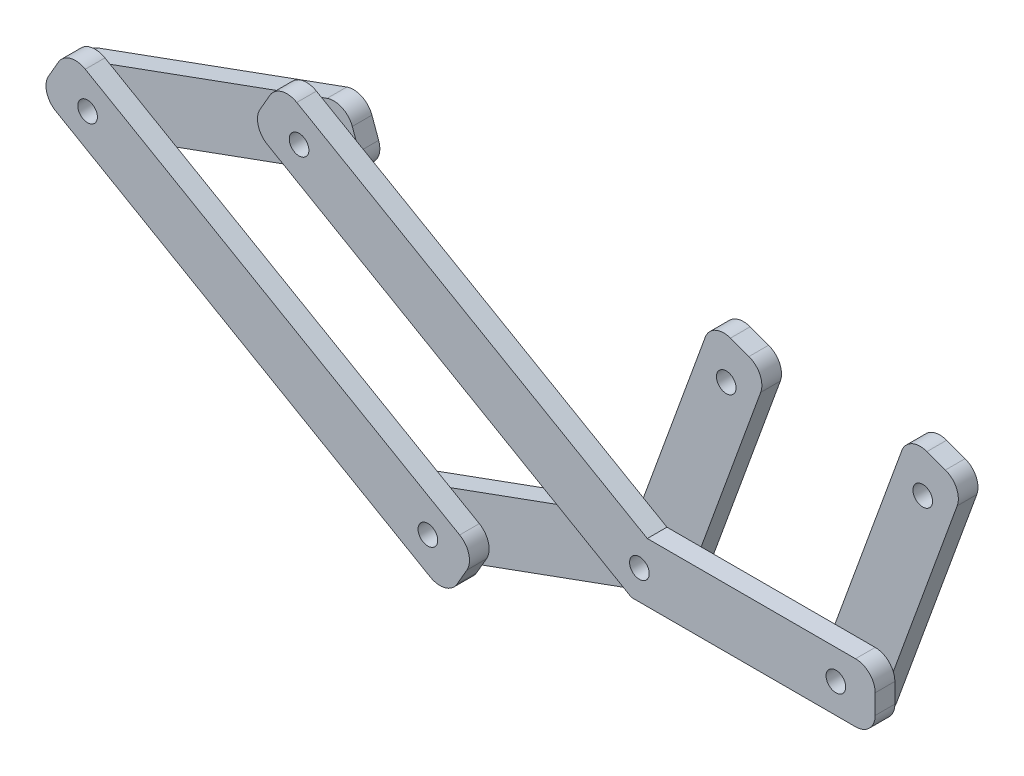
SolidWorks part; units mm, degrees
ref_plane "Front Plane" through (0, 0, 0) normal (0, 0, 1) x (1, 0, 0)
ref_plane "Top Plane" through (0, 0, 0) normal (0, 1, 0) x (1, 0, 0)
ref_plane "Right Plane" through (0, 0, 0) normal (1, 0, 0) x (0, 0, -1)
sketch "Sketch1" plane through (0, 0, 0) normal (0, 0, 1) x (1, 0, 0)
  line L0 (0, 0) -> (-34.202, -93.9693)
  line L1 (0, 0) -> (100, 0)
  line L2 (100, 0) -> (65.798, -93.9693)
  line L8 (65.798, -93.9693) -> (-34.202, -93.9693)
  line L19 (0, 0) -> (68.404, 187.9385)
  line L20 (0, 0) -> (-173.2051, 100)
  line L21 (-34.202, -93.9693) -> (-207.4071, 6.0307)
  line L22 (-34.202, -93.9693) -> (-141.8362, -133.1449)
  line L23 (-141.8362, -133.1449) -> (-315.0412, -33.1449)
  line L24 (-315.0412, -33.1449) -> (-207.4071, 6.0307)
  line L25 (-261.2242, -13.5571) -> (-287.4244, 58.4276)
  line L26 (-287.4244, 58.4276) -> (-173.2051, 100)
  line L27 (-207.4071, 6.0307) -> (-97.22, 46.1356)
  circle A4 centre (-173.2051, 100) radius 48.0396
  dimension "D6" = 200
  dimension "D8" = 130
  dimension "D9" = 150
  dimension "D10" = 96.0793
  dimension "D1" = 200
  dimension "D2" = 110
  dimension "D3" = 100
  dimension "D4" = 200
  dimension "D5" = 100
  dimension "D7" = 200
ref_plane "Plane1" through (0, 0, 180) normal (0, 0, 1) x (1, 0, 0)
sketch "Sketch2" plane through (0, 0, 180) normal (0, 0, 1) x (1, 0, 0)
  line L9 (2.1419, 20.504) -> (11.5389, 17.0838)
  line L10 (-10.6752, 14.5272) -> (-45.9051, -82.2662)
  line L11 (17.5156, 4.2666) -> (-22.4989, -105.6724)
  line L13 (-162.3401, -135.2868) -> (-158.9199, -144.6837)
  line L14 (-156.3634, -122.4697) -> (-45.9051, -82.2662)
  line L15 (-146.1028, -150.6605) -> (-22.4989, -105.6724)
  line L19 (-34.202, -93.9693) -> (-141.8362, -133.1449) construction
  line L20 (0, 0) -> (-34.202, -93.9693) construction
  arc A2 (-146.1028, -150.6605) -> (-158.9199, -144.6837) centre (-149.523, -141.2635) cw
  arc A3 (-162.3401, -135.2868) -> (-156.3634, -122.4697) centre (-152.9432, -131.8666) cw
  arc A4 (-10.6752, 14.5272) -> (2.1419, 20.504) centre (-1.2783, 11.107) cw
  arc A5 (17.5156, 4.2666) -> (11.5389, 17.0838) centre (8.1187, 7.6868) ccw
  circle A6 centre (0, 0) radius 5
  circle A7 centre (-34.202, -93.9693) radius 5
  circle A8 centre (-141.8362, -133.1449) radius 5
  dimension "D4" = 15
  dimension "D1" = 10
  dimension "D5" = 10
  dimension "D9" = 10
  dimension "D10" = 10
  dimension "D2" = 20
  dimension "D3" = 15
  dimension "D6" = 20
  dimension "D7" = 15
  dimension "D8" = 15
extrude "Boss-Extrude1" add sketch "Sketch2" along normal blind 10
move or copy body "Body-Move/Copy1" bodies to move or copy 101 copy no translate (270, 0, 0)
ref_plane "Plane2" through (0, 0, 190) normal (0, 0, 1) x (1, 0, 0)
sketch "Sketch5" plane through (0, 0, 190) normal (0, 0, 1) x (1, 0, 0)
  line L0 (102.1419, 20.504) -> (111.5389, 17.0838)
  line L1 (89.3248, 14.5272) -> (48.2824, -98.2359)
  line L2 (117.5156, 4.2666) -> (76.4732, -108.4965)
  line L3 (54.2591, -111.053) -> (63.656, -114.4732)
  line L4 (100, 0) -> (65.798, -93.9693) construction
  arc A0 (76.4732, -108.4965) -> (63.656, -114.4732) centre (67.0762, -105.0763) cw
  arc A1 (48.2824, -98.2359) -> (54.2591, -111.053) centre (57.6793, -101.6561) ccw
  arc A2 (89.3248, 14.5272) -> (102.1419, 20.504) centre (98.7217, 11.107) cw
  arc A3 (111.5389, 17.0838) -> (117.5156, 4.2666) centre (108.1187, 7.6868) cw
  circle A4 centre (100, 0) radius 5
  circle A5 centre (65.798, -93.9693) radius 5
  dimension "D5" = 10
  dimension "D6" = 10
  dimension "D7" = 10
  dimension "D1" = 20
  dimension "D2" = 20
  dimension "D3" = 15
  dimension "D4" = 15
extrude "Boss-Extrude2" add sketch "Sketch5" along normal blind 10 separate body
move or copy body "Body-Move/Copy2" bodies to move or copy 103 copy no translate (270, 0, -10)
sketch "Sketch7" plane through (0, 0, 190) normal (0, 0, 1) x (1, 0, 0)
  line L0 (85.798, -88.9693) -> (85.798, -98.9693)
  line L1 (75.798, -78.9693) -> (-30.1828, -78.9693)
  line L2 (75.798, -108.9693) -> (-38.2213, -108.9693)
  line L4 (-222.2276, 20.3609) -> (-227.2276, 11.7006)
  line L5 (-208.5673, 24.0211) -> (-30.1828, -78.9693)
  line L6 (-223.5673, -1.9596) -> (-38.2213, -108.9693)
  line L9 (65.798, -93.9693) -> (-34.202, -93.9693) construction
  line L10 (-34.202, -93.9693) -> (-207.4071, 6.0307) construction
  circle A0 centre (65.798, -93.9693) radius 5
  circle A1 centre (-34.202, -93.9693) radius 5
  circle A2 centre (-207.4071, 6.0307) radius 5
  arc A3 (-227.2276, 11.7006) -> (-223.5673, -1.9596) centre (-218.5673, 6.7006) ccw
  arc A4 (-208.5673, 24.0211) -> (-222.2276, 20.3609) centre (-213.5673, 15.3609) ccw
  arc A5 (85.798, -98.9693) -> (75.798, -108.9693) centre (75.798, -98.9693) cw
  arc A6 (75.798, -78.9693) -> (85.798, -88.9693) centre (75.798, -88.9693) cw
  dimension "D3" = 10
  dimension "D4" = 10
  dimension "D9" = 10
  dimension "D10" = 10
  dimension "D1" = 15
  dimension "D2" = 20
  dimension "D5" = 20
  dimension "D6" = 15
  dimension "D7" = 15
  dimension "D8" = 15
extrude "Boss-Extrude3" add sketch "Sketch7" along normal blind 10 separate body
move or copy body "Body-Move/Copy3" bodies to move or copy 105 copy no translate (270, 0, 0)
sketch "Sketch8" plane through (0, 0, 190) normal (0, 0, 1) x (1, 0, 0)
  line L0 (-329.8617, -18.8148) -> (-334.8617, -27.475)
  line L1 (-316.2015, -15.1545) -> (-125.6759, -125.1545)
  line L2 (-331.2015, -41.1353) -> (-140.6759, -151.1353)
  line L3 (-122.0156, -138.8148) -> (-127.0156, -147.475)
  line L4 (-141.8362, -133.1449) -> (-315.0412, -33.1449) construction
  circle A0 centre (-141.8362, -133.1449) radius 5
  circle A1 centre (-315.0412, -33.1449) radius 5
  arc A2 (-140.6759, -151.1353) -> (-127.0156, -147.475) centre (-135.6759, -142.475) ccw
  arc A3 (-125.6759, -125.1545) -> (-122.0156, -138.8148) centre (-130.6759, -133.8148) cw
  arc A4 (-334.8617, -27.475) -> (-331.2015, -41.1353) centre (-326.2015, -32.475) ccw
  arc A5 (-316.2015, -15.1545) -> (-329.8617, -18.8148) centre (-321.2015, -23.8148) ccw
  dimension "D5" = 10
  dimension "D6" = 10
  dimension "D7" = 10
  dimension "D1" = 20
  dimension "D2" = 20
  dimension "D3" = 15
  dimension "D4" = 15
extrude "Boss-Extrude4" add sketch "Sketch8" along normal blind 10 separate body
move or copy body "Body-Move/Copy5" bodies to move or copy 108 copy no translate (270, 0, 0)
sketch "Sketch11" plane through (0, 0, 180) normal (0, 0, 1) x (1, 0, 0)
  line L0 (-335.5452, -35.2868) -> (-332.125, -44.6837)
  line L1 (-329.5685, -22.4697) -> (-203.1405, 23.5463)
  line L2 (-319.3079, -50.6605) -> (-192.8799, -4.6444)
  line L3 (-190.3233, 17.5696) -> (-186.9031, 8.1727)
  line L4 (-315.0412, -33.1449) -> (-207.4071, 6.0307) construction
  circle A0 centre (-315.0412, -33.1449) radius 5
  circle A1 centre (-207.4071, 6.0307) radius 5
  arc A2 (-203.1405, 23.5463) -> (-190.3233, 17.5696) centre (-199.7203, 14.1494) cw
  arc A3 (-192.8799, -4.6444) -> (-186.9031, 8.1727) centre (-196.3001, 4.7525) ccw
  arc A4 (-332.125, -44.6837) -> (-319.3079, -50.6605) centre (-322.7281, -41.2635) ccw
  arc A5 (-329.5685, -22.4697) -> (-335.5452, -35.2868) centre (-326.1483, -31.8666) ccw
  dimension "D5" = 10
  dimension "D6" = 10
  dimension "D7" = 10
  dimension "D1" = 15
  dimension "D2" = 15
  dimension "D3" = 20
  dimension "D4" = 20
extrude "Boss-Extrude5" add sketch "Sketch11" along normal blind 10 separate body
move or copy body "Body-Move/Copy6" bodies to move or copy 110 copy no translate (270, 0, 0)
